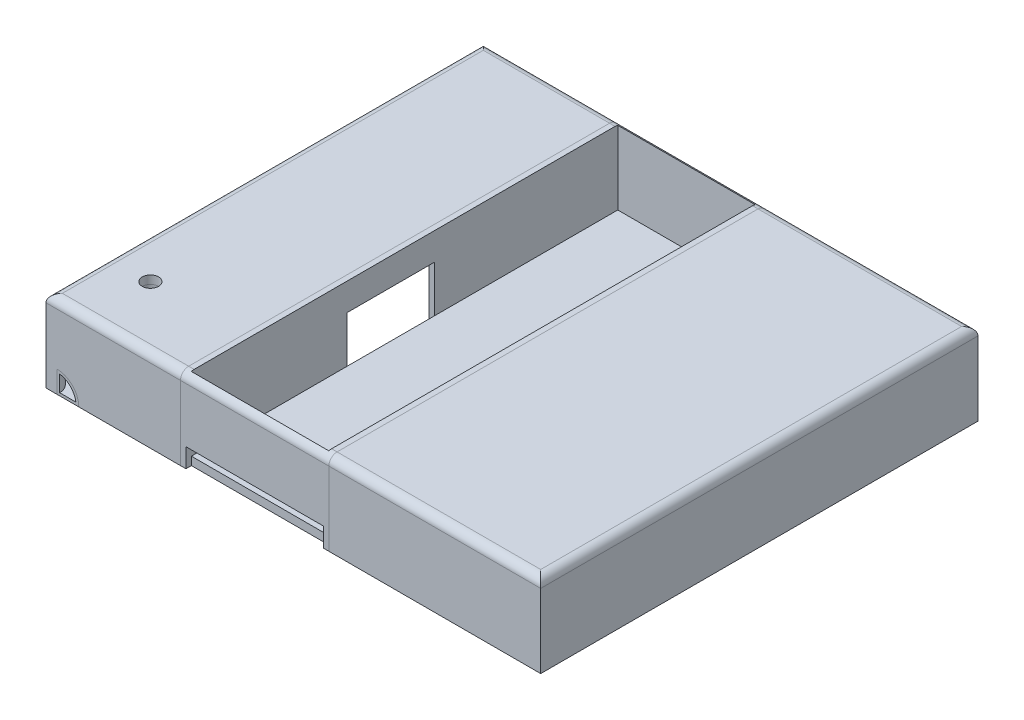
SolidWorks part; units mm, degrees
ref_plane "Front Plane" through (0, 0, 0) normal (0, 0, 1) x (1, 0, 0)
ref_plane "Top Plane" through (0, 0, 0) normal (0, 1, 0) x (1, 0, 0)
ref_plane "Right Plane" through (0, 0, 0) normal (1, 0, 0) x (0, 0, -1)
sketch3d "3DSketch2"
  line L0 (-19.15, 29.25, -28.4) -> (5, 23.2287, -28.4) construction
  dimension "D1" = 0
sketch "Sketch1" plane through (0, 0, 0) normal (0, 1, 0) x (1, 0, 0)
  line L1 (-45.25, -40) -> (45.25, -40)
  line L2 (-45.25, -40) -> (-45.25, 40)
  line L3 (-45.25, 40) -> (45.25, 40)
  line L4 (45.25, -40) -> (45.25, 40)
  line L5 (-45.25, -40) -> (45.25, 40) construction
  line L6 (-45.25, 40) -> (45.25, -40) construction
  point P0 (0, 0)
  dimension "D1" = 80
  dimension "D2" = 90.5
extrude "Boss-Extrude1" add sketch "Sketch1" along normal blind 15
shell "Shell3" thickness 1.5 removed face at (0, 0, 0)
sketch "Sketch4" plane through (-45.25, 0, 0) normal (-1, 0, 0) x (0, 0, 1)
  line L0 (-34.38, 1.6) -> (-28.48, 1.6) construction
  line L1 (-34.38, 3.3) -> (-28.48, 3.3)
  line L2 (-34.38, -0.1) -> (-28.48, -0.1)
  line L3 (-40, 15) -> (-40, 0) construction
  arc A0 (-34.38, 3.3) -> (-34.38, -0.1) centre (-34.38, 1.6) ccw
  arc A1 (-28.48, -0.1) -> (-28.48, 3.3) centre (-28.48, 1.6) ccw
  point P2 (-31.43, 1.6)
  dimension "D1" = 8.57
  dimension "D2" = 5.9
  dimension "D3" = 3.4
extrude "Cut-Extrude2" cut sketch "Sketch4" against normal blind 1.5
sketch "Sketch6" plane through (-45.25, 0, 0) normal (-1, 0, 0) x (0, 0, 1)
  line L0 (-27.9055, 0) -> (40, 0) construction
  line L1 (-24.4, 7.3) -> (-10.75, 7.3)
  line L2 (-24.4, 7.3) -> (-24.4, 0)
  line L3 (-24.4, 0) -> (-10.75, 0)
  line L4 (-10.75, 7.3) -> (-10.75, 0)
  line L5 (-24.4, 7.3) -> (-10.75, 0) construction
  line L6 (-24.4, 0) -> (-10.75, 7.3) construction
  line L8 (-40, 15) -> (-40, 0) construction
  point P6 (-17.575, 3.65)
  dimension "D1" = 7.3
  dimension "D2" = 13.65
  dimension "D3" = 0
  dimension "D4" = 22.425
extrude "Cut-Extrude3" cut sketch "Sketch6" against normal blind 1.5
sketch "Sketch9" plane through (-45.25, 0, 0) normal (-1, 0, 0) x (0, 0, 1)
  line L0 (-27.9055, 0) -> (-24.4, 0) construction
  line L1 (-25.4, 0) -> (-9.75, 0)
  line L2 (-25.4, 0) -> (-25.4, 1)
  line L3 (-25.4, 1) -> (-9.75, 1)
  line L4 (-9.75, 0) -> (-9.75, 1)
  line L5 (-10.75, 0) -> (-10.75, 7.3) construction
  line L7 (-24.4, 7.3) -> (-24.4, 0) construction
  dimension "D1" = 1
  dimension "D2" = 1
  dimension "D3" = 1
extrude "Boss-Extrude2" add sketch "Sketch9" along normal blind 1.5
sketch "Sketch11" plane through (0, 15, 0) normal (0, 1, 0) x (1, 0, 0)
  line L1 (-45.25, 40) -> (-45.25, -40) construction
  circle A0 centre (-37.55, -28.6) radius 1.5
  dimension "D1" = 7.7
fillet "Fillet7" radius 1.5 4 edges at (45.25, 15, 0) (0, 15, 40) (0, 15, -40) (-45.25, 15, 0)
extrude "Boss-Extrude10" add sketch "Sketch11" against normal blind 11
extrude "Cut-Extrude10" cut sketch "Sketch11<3>" against normal blind 1.5
sketch "Sketch11<3>" plane through (0, 15, 0) normal (0, 1, 0) x (1, 0, 0) same geometry as "Sketch11"
shell "Shell9" thickness 1 removed face at (-37.55, 4, 30.1) removed face at (-37.55, 13.5, 30.1) outward yes
sketch "Sketch33" plane through (0, 0, 40) normal (0, 0, 1) x (1, 0, 0)
  line L3 (-45.25, 0) -> (45.25, 0) construction
  line L6 (-43.25, 4) -> (-43.25, 0)
  line L7 (-43.25, 0) -> (-39.25, 0)
  arc A2 (-43.25, 4) -> (-39.25, 0) centre (-43.25, 0) cw
  dimension "D1" = 2
revolve "Cut-Revolve4" cut sketch "Sketch33" angle 90 about axis through (-45.25, 15, 40) along (0, -1, 0) reverse direction yes
revolve "Revolve3" add sketch "Sketch33<2>" angle 90 about axis through (-45.25, 15, 40) along (0, -1, 0) reverse direction yes
sketch "Sketch33<2>" plane through (0, 0, 40) normal (0, 0, 1) x (1, 0, 0) same geometry as "Sketch33"
shell "Shell14" thickness 0.5 removed face at (-45.25, 1.6095, 36.3905) removed face at (-41.6405, 1.6095, 40)
sketch "Sketch45" plane through (5.7452, 23.0429, 0) normal (-0.2419, -0.9703, 0) x (-0.9703, 0.2419, 0)
  line L5 (-40.5397, -40) -> (-19.0325, -40)
  line L6 (-40.5397, -40) -> (-40.5397, 40)
  line L7 (-40.5397, 40) -> (-19.0325, 40)
  line L8 (-19.0325, -40) -> (-19.0325, 40)
sketch "Sketch47" plane through (0, 0, 40) normal (0, 0, 1) x (1, 0, 0)
  line L0 (-43.75, 15) -> (43.75, 15) construction
  line L1 (-20.65, 0) -> (6.5, 0)
  line L2 (-20.65, 0) -> (-20.65, 15)
  line L3 (-20.65, 15) -> (6.5, 15)
  line L4 (6.5, 0) -> (6.5, 15)
  line L5 (-45.25, 13.5) -> (-45.25, 0) construction
  line L6 (-39.25, 0) -> (45.25, 0) construction
  dimension "D1" = 27.15
  dimension "D2" = 24.6
  dimension "D3" = 0
extrude "Cut-Extrude15" cut sketch "Sketch47" against normal through all
extrude "Boss-Extrude12" add sketch "Sketch47<2>" against normal blind 80 separate body
sketch "Sketch47<2>" plane through (0, 0, 40) normal (0, 0, 1) x (1, 0, 0) same geometry as "Sketch47"
shell "Shell15" thickness 1 removed face at (-7.075, 15, 0)
fillet "Fillet13" radius 1.5 2 edges at (-7.075, 15, -40) (-7.075, 15, 40)
sketch "Sketch52" plane through (0, 0, 39) normal (0, 0, -1) x (-1, 0, 0)
  line L0 (19.65, 14.9142) -> (19.65, 1.5) construction
  line L1 (-5.5, 0) -> (19.65, 0)
  line L2 (-5.5, 0) -> (-5.5, 3.5)
  line L3 (-5.5, 3.5) -> (19.65, 3.5)
  line L4 (19.65, 0) -> (19.65, 3.5)
  line L5 (19.65, 14.9142) -> (19.65, 1.5) construction
  line L6 (19.65, 14.9142) -> (-5.5, 14.9142) construction
  dimension "D1" = 25.15
  dimension "D2" = 11.4142
extrude "Cut-Extrude21" cut sketch "Sketch52" against normal blind 1
sketch "Sketch54" plane through (-19.65, 0, 0) normal (1, 0, 0) x (0, 0, -1)
  line L0 (-39, 0) -> (-40, 0) construction
  line L5 (5.5, 10) -> (-10.5, 10)
  line L6 (5.5, 10) -> (5.5, 0)
  line L7 (5.5, 0) -> (-10.5, 0)
  line L8 (-10.5, 10) -> (-10.5, 0)
  line L9 (5.5, 10) -> (-10.5, 0) construction
  line L10 (5.5, 0) -> (-10.5, 10) construction
  line L12 (40, 13.5) -> (40, 0) construction
  line L13 (-40, 13.5) -> (-40, 0) construction
  point P0 (-2.5, 5)
  dimension "D1" = 10
  dimension "D2" = 34.5
  dimension "D3" = 29.5
extrude "Cut-Extrude22" cut sketch "Sketch54" against normal blind 1
